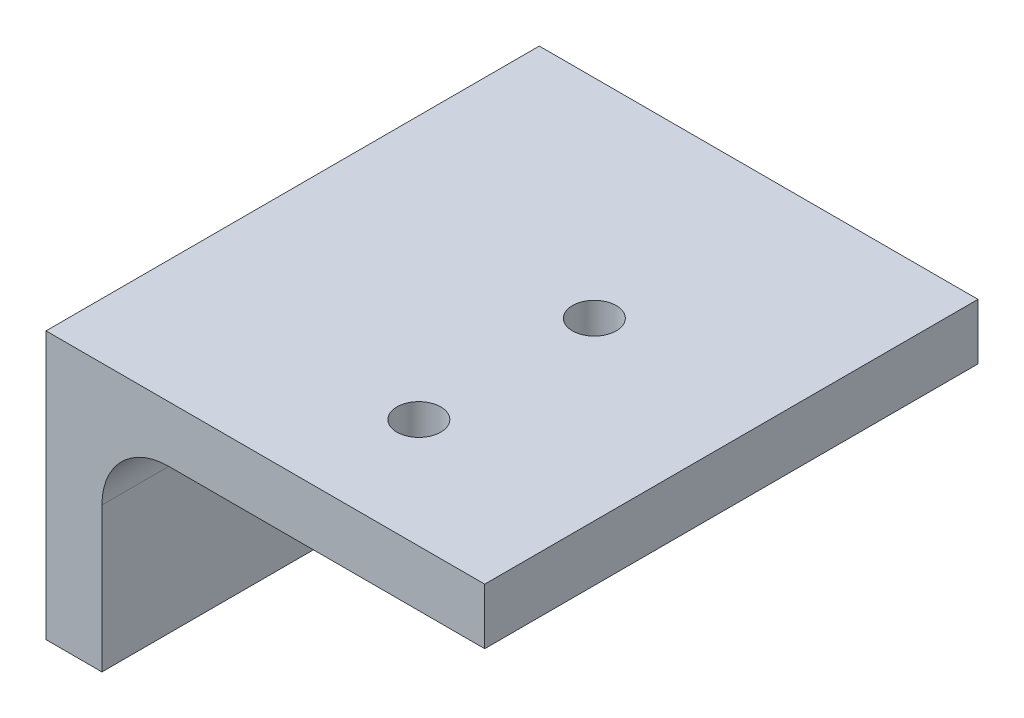
SolidWorks part; units mm, degrees
ref_plane "Front Plane" through (0, 0, 0) normal (0, 0, 1) x (1, 0, 0)
ref_plane "Top Plane" through (0, 0, 0) normal (0, 1, 0) x (1, 0, 0)
ref_plane "Right Plane" through (0, 0, 0) normal (1, 0, 0) x (0, 0, -1)
sketch "Sketch1" plane through (0, 0, 0) normal (0, 0, 1) x (1, 0, 0)
  line L0 (45.33, -6.4) -> (45.33, -36.88)
  line L1 (45.33, -36.88) -> (51.7054, -36.88)
  line L2 (51.7054, -36.88) -> (51.7054, -20.3954)
  line L3 (59.3254, -12.7754) -> (95.33, -12.7754)
  line L4 (95.33, -12.7754) -> (95.33, -6.4)
  line L5 (115, -6.4) -> (-15, -6.4) construction
  line L6 (95.33, -6.4) -> (45.33, -6.4)
  line L7 (45.33, 0) -> (45.33, 1000) construction
  arc A0 (59.3254, -12.7754) -> (51.7054, -20.3954) centre (59.3254, -20.3954) ccw
  dimension "D3" = 7.62
  dimension "D1" = 6.3754
  dimension "D2" = 6.3754
  dimension "D4" = 30.48
  dimension "D5" = 50
extrude "Boss-Extrude1" add sketch "Sketch1" against normal blind 56.22
sketch "Sketch2" plane through (0, -6.4, 0) normal (0, 1, 0) x (1, 0, 0)
  circle A0 centre (75.33, 12.4936) radius 2.5
  circle A1 centre (75.33, 32.4936) radius 2.5
extrude "Cut-Extrude1" cut sketch "Sketch2" against normal through all
sketch "Sketch4" plane through (45.33, 0, 0) normal (-1, 0, 0) x (0, 0, 1)
  line L0 (-56.22, -6.4) -> (-56.22, -36.88) construction
  line L1 (-56.22, -6.4) -> (0, -6.4) construction
  circle A0 centre (-32.598, -24.18) radius 2.5
  dimension "D2" = 5
  dimension "D1" = 23.622
  dimension "D3" = 17.78
extrude "Cut-Extrude2" cut sketch "Sketch4" against normal through all
